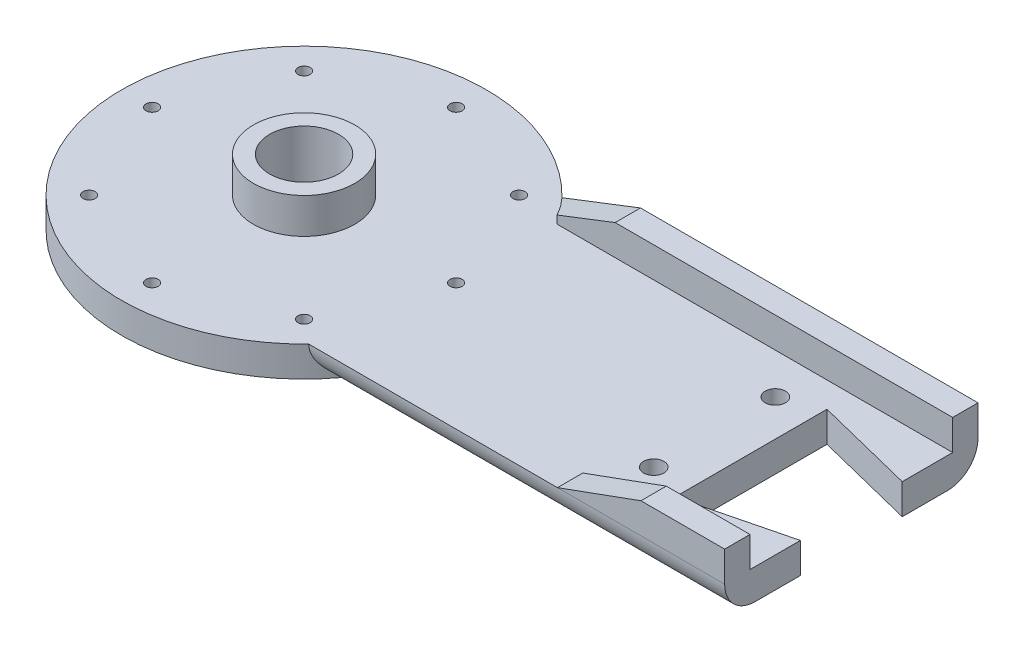
SolidWorks part; units mm, degrees
ref_plane "Alzado" through (0, 0, 0) normal (0, 0, 1) x (1, 0, 0)
ref_plane "Planta" through (0, 0, 0) normal (0, 1, 0) x (1, 0, 0)
ref_plane "Vista lateral" through (0, 0, 0) normal (1, 0, 0) x (0, 0, -1)
sketch "Croquis1" plane through (0, 0, 0) normal (0, 1, 0) x (1, 0, 0)
  line L0 (36.7465, 5.1531) -> (36.7465, 12.6281)
  line L1 (36.7465, 12.6281) -> (-4.3081, 12.6281)
  line L2 (36.7465, -4.8969) -> (36.7465, -12.3719)
  line L3 (36.7465, -12.3719) -> (-4.2999, -12.3719)
  line L4 (36.7465, -4.8969) -> (26.8465, -7.3719)
  line L5 (26.8465, -7.3719) -> (26.8465, 7.6281)
  line L6 (26.8465, 7.6281) -> (36.7465, 5.1531)
  arc A0 (-4.3081, 12.6281) -> (-4.2999, -12.3719) centre (-17.2583, 0.1239) ccw
  circle A1 centre (-17.2535, 0.1281) radius 3.4
  circle A2 centre (-17.2535, 15.1281) radius 0.6
  circle A3 centre (23.2465, 6.1281) radius 1
  circle A4 centre (23.2465, -5.8719) radius 1
  circle A5 centre (-6.6469, 10.7347) radius 0.6
  circle A6 centre (-2.2535, 0.1281) radius 0.6
  circle A7 centre (-6.6469, -10.4785) radius 0.6
  circle A8 centre (-17.2535, -14.8719) radius 0.6
  circle A9 centre (-27.8601, -10.4785) radius 0.6
  circle A10 centre (-32.2535, 0.1281) radius 0.6
  circle A11 centre (-27.8601, 10.7347) radius 0.6
  point P31 (-17.2535, 0.1281)
extrude "Saliente-Extruir1" add sketch "Croquis1" along normal blind 3
sketch "Croquis2" plane through (0, 3, 0) normal (0, 1, 0) x (1, 0, 0)
  line L1 (36.7465, 12.6281) -> (-4.3081, 12.6281)
  line L2 (36.7465, 12.6281) -> (36.7465, 10.1281)
  line L3 (36.7465, 10.1281) -> (-2.2924, 10.1281)
  line L5 (36.7465, -12.3719) -> (20.2465, -12.3719)
  line L6 (36.7465, -12.3719) -> (36.7465, -9.8719)
  line L7 (36.7465, -9.8719) -> (20.2465, -9.8719)
  line L8 (20.2465, -12.3719) -> (20.2465, -9.8719)
  arc A0 (-2.2924, 10.1281) -> (-4.3081, 12.6281) centre (-17.2535, 0.1281) ccw
  dimension "D1" = 2.5
  dimension "D2" = 16.5
extrude "Saliente-Extruir2" add sketch "Croquis2" along normal blind 3
sketch "Croquis3" plane through (0, 0, 12.3719) normal (0, 0, 1) x (1, 0, 0)
  line L0 (20.2465, 3) -> (28.4865, 6)
  line L1 (20.2465, 6) -> (36.7465, 6) construction
  line L2 (28.4865, 6) -> (20.2465, 6)
  line L3 (20.2465, 6) -> (20.2465, 3)
  dimension "D1" = 8.24
extrude "Cortar-Extruir1" cut sketch "Croquis3" against normal blind 3
sketch "Croquis4" plane through (0, 0, -12.6281) normal (0, 0, -1) x (-1, 0, 0)
  line L0 (4.3081, 3) -> (4.3081, 6)
  line L1 (4.3081, 6) -> (-3.4419, 6)
  line L2 (-36.7465, 6) -> (4.3081, 6) construction
  line L3 (-3.4419, 6) -> (4.3081, 3)
  dimension "D1" = 7.75
extrude "Cortar-Extruir2" cut sketch "Croquis4" against normal blind 3
sketch "Croquis5" plane through (0, 3, 0) normal (0, 1, 0) x (1, 0, 0)
  circle A0 centre (-17.2535, 0.1281) radius 5
  circle A1 centre (-17.2535, 0.1281) radius 3.4 construction
  circle A2 centre (-17.2535, 0.1281) radius 3.4
  dimension "D1" = 10
extrude "Saliente-Extruir3" add sketch "Croquis5" along normal blind 3.5
fillet "Redondeo1" radius 3 2 edges at (16.2192, 0, -12.6281) (16.2233, 0, 12.3719)
